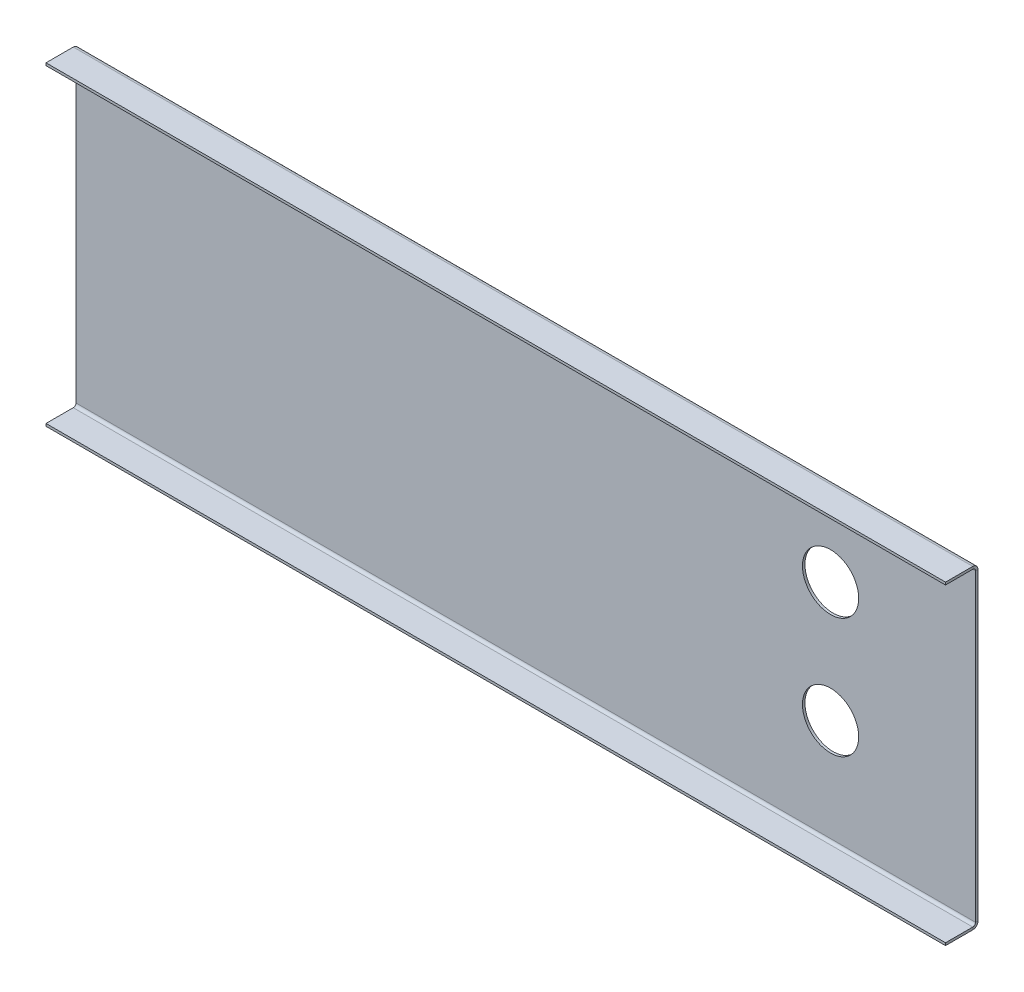
SolidWorks part; units mm, degrees
note: The reader was unsure of these and kept them because the rebuilt part matched: flange length of "Ребро-кромка1".
ref_plane "Спереди" through (0, 0, 0) normal (0, 0, 1) x (1, 0, 0)
ref_plane "Сверху" through (0, 0, 0) normal (0, 1, 0) x (1, 0, 0)
ref_plane "Справа" through (0, 0, 0) normal (1, 0, 0) x (0, 0, -1)
sketch "Эскиз1" plane through (0, 0, 0) normal (0, 0, 1) x (1, 0, 0)
  line L1 (-57.7, 25.5473) -> (302.3, 25.5473)
  line L2 (-57.7, 25.5473) -> (-57.7, -98.4527)
  line L3 (-57.7, -98.4527) -> (302.3, -98.4527)
  line L4 (302.3, 25.5473) -> (302.3, -98.4527)
  dimension "D1" = 360
  dimension "D2" = 124
sheet metal parameters "Листовой металл1" thickness 1 parameters "D1"=1.1
base flange "Базовая кромка1" sketch "Эскиз1" thickness 1 reverse thickness direction no parameters "D1"=1.1
edge flange "Ребро-кромка1" sketch "Эскиз6" flange profiles "Эскиз6", "Эскиз7" flange angle 90 flange length 12 flange position material outside bend radius 1.1 thickness 1 relief rectangular parameters "D6"=10, "D8"=1
sketch "Эскиз6" plane through (0, 25.5473, 0) normal (0, 1, 0) x (-1, 0, 0)
  line L2 (-302.3, 0) -> (-302.3, 12)
  line L3 (-302.3, 12) -> (57.7, 12)
  line L4 (57.7, 12) -> (57.7, 0)
  line L5 (-302.3, 0) -> (57.7, 0) construction
  line L6 (-302.3, 0) -> (57.7, 0)
sketch "Эскиз7" plane through (0, -98.4527, 0) normal (0, -1, 0) x (1, 0, 0)
  line L2 (-57.7, 0) -> (-57.7, 12)
  line L3 (-57.7, 12) -> (302.3, 12)
  line L4 (302.3, 12) -> (302.3, 0)
  line L5 (-57.7, 0) -> (302.3, 0) construction
  line L6 (-57.7, 0) -> (302.3, 0)
bend "EdgeBend1" bend radius 1.1 bend angle 90 parameters "D5"=1
bend "EdgeBend2" bend radius 1.1 bend angle 90 parameters "D5"=2
sketch "Эскиз8" plane through (0, 0, -1) normal (0, 0, -1) x (-1, 0, 0)
  line L0 (-244.3, 24.4473) -> (-244.3, -123.984) construction
  line L1 (57.7, 24.4473) -> (-302.3, 24.4473) construction
  line L2 (-302.3, -97.3527) -> (-302.3, 24.4473) construction
  line L3 (57.7, 26.5473) -> (-302.3, 26.5473) construction
  circle A0 centre (-244.3, -8.4527) radius 11.25
  circle A1 centre (-244.3, -56.4527) radius 11.25
  dimension "D2" = 48
  dimension "D3" = 35
  dimension "D4" = 22.5
  dimension "D5" = 22.5
  dimension "D1" = 58
extrude "Вырез-Вытянуть1" cut sketch "Эскиз8" against normal blind 10 normal cut yes
flat pattern "Развертка1" [suppressed]
sketch "Сгиб-Линии1" plane through (0, 0, 0) normal (0, 1, 0) x (1, 0, 0)
sketch3d "Граничная рамка1" [suppressed]
  line L0 (57.7, -88.4527, 0) -> (-251.3, -88.4527, 0) construction
  line L1 (57.7, 25.5473, 0) -> (-251.3, 25.5473, 0) construction
  line L2 (57.7, -88.4527, 0) -> (57.7, 25.5473, 0) construction
  line L3 (-251.3, -88.4527, 0) -> (-251.3, 25.5473, 0) construction
bend of the flat pattern "Плоское состояние-<EdgeBend1>1"
bend of the flat pattern "Плоское состояние-<EdgeBend2>1"
